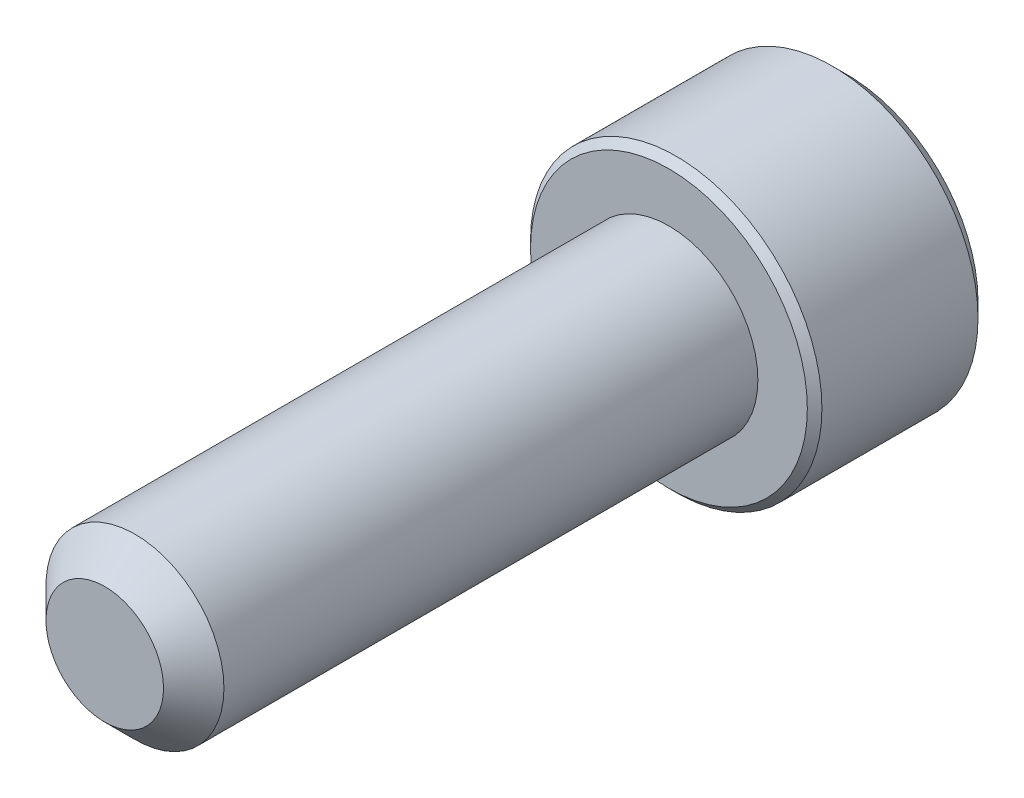
SolidWorks part; units mm, degrees
material "AISI 304"
ref_plane "Front Plane" through (0, 0, 0) normal (0, 0, 1) x (1, 0, 0)
ref_plane "Top Plane" through (0, 0, 0) normal (0, 1, 0) x (1, 0, 0)
ref_plane "Right Plane" through (0, 0, 0) normal (1, 0, 0) x (0, 0, -1)
sketch "Sketch0" plane through (0, 0, 0) normal (1, 0, 0) x (0, 0, -1)
  line L0 (0, 0) -> (11.1125, 0) construction
  point P2 (14.6177, 0)
  point P4 (0, 0)
  dimension "D1" = 11.1125
  dimension "D2" = 3.5052
  dimension "Min Thread" = 0
sketch "Sketch1" plane through (0, 0, 0) normal (0, 0, 1) x (1, 0, 0)
  circle A0 centre (0, 0) radius 1.7526
  dimension "OD" = 3.5052
extrude "Extrude1" add sketch "Sketch1" against normal blind 11.1125
sketch "Sketch2" plane through (0, 0, 0) normal (0, 0, 1) x (1, 0, 0)
  circle A0 centre (0, 0) radius 1.7526 construction
  circle A1 centre (0, 0) radius 1.7526
curve "Helix/Spiral1" pitch 0.7937 height 11.9062 turns 15 parameters "pitch"=0.7937
chamfer "Chamfer3" distance 0.5953 angle 45 1 edges at (1.7526, 0, 0)
sketch "Sketch3" plane through (0, 0, 0) normal (1, 0, 0) x (0, 0, -1)
  line L0 (-0.6945, 1.7526) -> (-0.3969, 1.237)
  line L1 (-0.3969, 1.237) -> (-0.2977, 1.237)
  line L2 (-0.2977, 1.237) -> (0, 1.7526)
  line L3 (-0.6945, 1.7526) -> (0, 1.7526)
  line L4 (-0.3473, 1.7526) -> (-0.3473, 1.237) construction
  line L5 (-0.5457, 1.4948) -> (-0.1488, 1.4948) construction
  line L6 (0, 1.7526) -> (0, -1.7526) construction
  dimension "D1" = 0.0992
  dimension "D2" = 0.3969
  dimension "D3" = 60
sweep "Cut-Sweep1" [suppressed] cut profiles "Sketch3" path "Helix/Spiral1"
sketch "Sketch5" [suppressed] plane through (0, 0, 0) normal (1, 0, 0) x (0, 0, -1)
  line L0 (6.35, -1.2539) -> (6.35, 1.2505) construction
  line L1 (6.35, 1.7526) -> (0, 1.7526)
  line L2 (6.35, 1.7526) -> (6.35, 0)
  line L3 (6.35, 0) -> (-0.6379, 0)
  line L4 (0, 0) -> (6.35, 0) construction
  line L5 (0, 1.7526) -> (-0.6379, 0)
  line L6 (0, 0) -> (8.89, 0) construction
  dimension "D1" = 70
  dimension "D3" = 2.54
revolve "partially thread" [suppressed] add sketch "Sketch5" angle 360 about L6
sketch "Sketch6" plane through (0, 0, -11.1125) normal (0, 0, -1) x (-1, 0, 0)
  circle A0 centre (0, 0) radius 2.8702
  dimension "head dia" = 5.7404
extrude "Extrude2" add sketch "Sketch6" along normal blind 3.5052
sketch "Sketch7" plane through (0, 0, -14.6177) normal (0, 0, -1) x (-1, 0, 0)
  line L1 (0, 1.604) -> (-1.3891, 0.802)
  line L2 (-1.3891, 0.802) -> (-1.3891, -0.802)
  line L3 (-1.3891, -0.802) -> (0, -1.604)
  line L4 (0, -1.604) -> (1.3891, -0.802)
  line L5 (1.3891, -0.802) -> (1.3891, 0.802)
  line L6 (1.3891, 0.802) -> (0, 1.604)
  circle A0 centre (0, 0) radius 1.3891 construction
  dimension "hex dia" = 2.7781
extrude "Cut-Extrude1" cut sketch "Sketch7" against normal blind 2.0836
sketch "Sketch8" plane through (0, 0, -14.6177) normal (0, 0, -1) x (-1, 0, 0)
  circle A0 centre (0, 0) radius 1.604
extrude "Cut-Extrude2" cut sketch "Sketch8" against normal through all draft 45
chamfer "Chamfer1" distance 0.287 angle 45 1 edges at (-2.8702, 0, -14.6177)
chamfer "Chamfer2" distance 0.1435 angle 45 1 edges at (-2.8702, 0, -11.1125)
sketch "Sketch9" plane through (0, 0, 0) normal (1, 0, 0) x (0, 0, -1)
  line L0 (0, 1.7526) -> (0, -1.7526) construction
  line L1 (1.9844, 1.7526) -> (1.9844, -1.7526) construction
  line L2 (14.6177, 2.8702) -> (14.6177, -2.8702) construction
  line L3 (11.1125, 2.8702) -> (11.1125, -2.8702) construction
  line L4 (11.1125, 2.7267) -> (11.1125, -2.7267) construction
  line L5 (14.6177, -2.5832) -> (14.6177, 2.5832) construction
  line L6 (11.1125, -2.8702) -> (11.1125, 2.8702) construction
  line L7 (0, 1.1573) -> (0, -1.1573) construction
  line L8 (-0.6945, 1.7526) -> (0, 1.7526) construction
  line L9 (1.9844, 0) -> (0, 0) construction
  dimension "D1" = 1.9844
equation "\"D3@Helix/Spiral1\" = \"screw length@Extrude1\"+\"pitch@Helix/Spiral1\""
equation "\"D1@Sketch3\" = \"pitch@Helix/Spiral1\"*.125"
equation "\"D2@Sketch3\" = \"pitch@Helix/Spiral1\"*.5"
equation "\"D1@Cut-Extrude1\" = \"hex dia@Sketch7\"*.75"
equation "\"D1@Chamfer1\" = \"head dia@Sketch6\"*.05"
equation "\"D1@Sketch9\" = \"pitch@Helix/Spiral1\"*2.50"
equation "\"D1@Chamfer2\" = \"D1@Chamfer1\"/2"
equation "\"D1@Chamfer3\" = \"pitch@Helix/Spiral1\"*.750"
equation "\"D1@Sketch0\" = \"screw length@Extrude1\""
equation "\"D2@Sketch0\" = \"head depth@Extrude2\""
